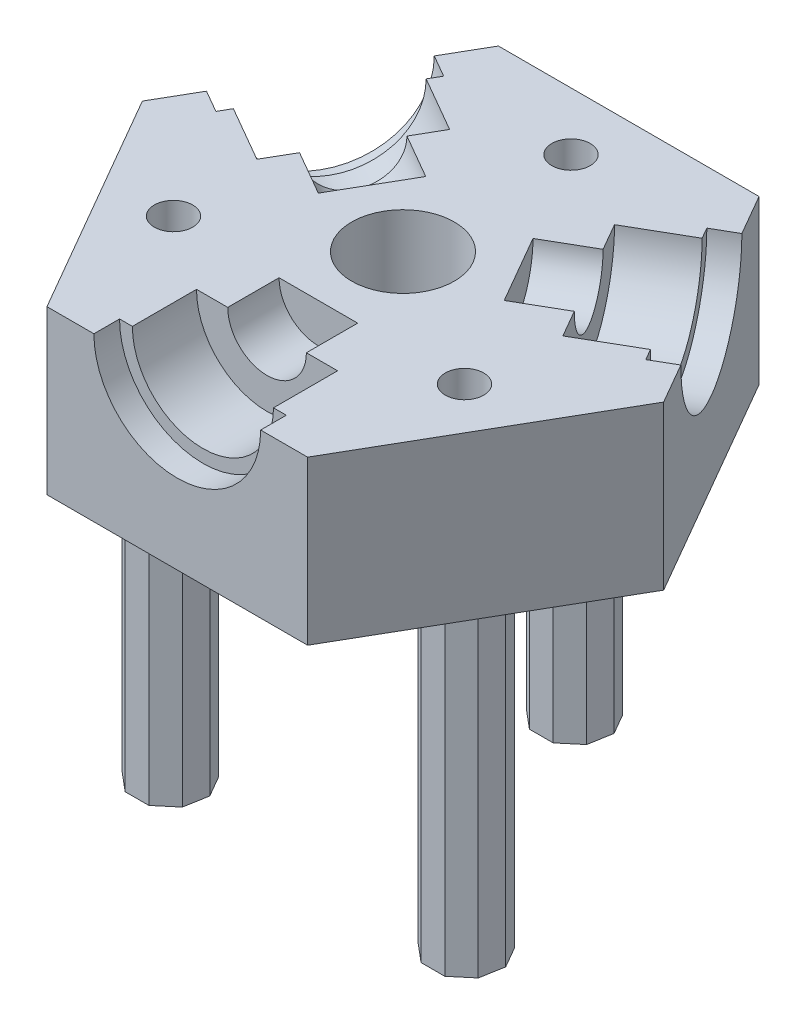
SolidWorks part; units mm, degrees
ref_plane "Front Plane" through (0, 0, 0) normal (0, 0, 1) x (1, 0, 0)
ref_plane "Top Plane" through (0, 0, 0) normal (0, 1, 0) x (1, 0, 0)
ref_plane "Right Plane" through (0, 0, 0) normal (1, 0, 0) x (0, 0, -1)
sketch "Sketch1" plane through (0, 0, 0) normal (0, 1, 0) x (1, 0, 0)
  line L1 (10.16, -17.5976) -> (20.32, 0)
  line L2 (20.32, 0) -> (10.16, 17.5976)
  line L3 (10.16, 17.5976) -> (-10.16, 17.5976)
  line L4 (-10.16, 17.5976) -> (-20.32, 0)
  line L5 (-20.32, 0) -> (-10.16, -17.5976)
  line L6 (-10.16, -17.5976) -> (10.16, -17.5976)
  circle A0 centre (0, 0) radius 17.5976 construction
  dimension "D1" = 20.32
extrude "Boss-Extrude1" add sketch "Sketch1" along normal blind 12.7 contours L4 L5 L6 L1 L2 L3
sketch "Sketch2" plane through (0, 0, 0) normal (0, -1, 0) x (1, 0, 0)
  circle A0 centre (0, 0) radius 4.1
  circle A1 centre (0, 0) radius 5.5
  dimension "D1" = 8.2
  dimension "D2" = 11
extrude "Boss-Extrude2" add sketch "Sketch2" along normal blind 3.5
sketch "Sketch5" plane through (0, 12.7, 0) normal (0, 1, 0) x (1, 0, 0)
  line L14 (0, -17.5976) -> (0, -6.5976)
  line L15 (-10.16, -17.5976) -> (10.16, -17.5976) construction
  line L16 (0, -6.5976) -> (-3.0653, -6.5976)
  line L17 (-3.0653, -6.5976) -> (-3.0653, -10.5976)
  line L18 (-3.0653, -10.5976) -> (-5.5, -10.5976)
  line L19 (-5.5, -10.5976) -> (-5.5, -15.5976)
  line L20 (-5.5, -15.5976) -> (-6.5, -15.5976)
  line L21 (-6.5, -15.5976) -> (-6.5, -17.5976)
  line L22 (-6.5, -17.5976) -> (0, -17.5976)
  dimension "D1" = 6.5
  dimension "D2" = 5.5
  dimension "D3" = 2
  dimension "D4" = 5
  dimension "D5" = 4
  dimension "D6" = 3.0653
revolve "Cut-Revolve1" cut sketch "Sketch5" angle 360 about L14
pattern_circular "CirPattern1" count 3 over 360 about axis through (0, -3.5, 0) along (0, 1, 0) of "Cut-Revolve1" reverse direction yes
sketch "Sketch6" plane through (0, 12.7, 0) normal (0, 1, 0) x (1, 0, 0)
  circle A0 centre (0, 0) radius 4
  dimension "D1" = 8
extrude "Cut-Extrude1" cut sketch "Sketch6" against normal through all
sketch "Random Circles" plane through (0, 12.7, 0) normal (0, 1, 0) x (1, 0, 0)
  line L0 (10.16, 17.5976) -> (-10.16, 17.5976) construction
  line L1 (-20.32, 0) -> (-10.16, -17.5976) construction
  line L2 (10.16, -17.5976) -> (20.32, 0) construction
  circle A0 centre (0, 13.0976) radius 1.5
  circle A1 centre (11.3429, -6.5488) radius 1.5
  circle A2 centre (-11.3429, -6.5488) radius 1.5
  point P11 (0, 0)
  dimension "D1" = 3
  dimension "D2" = 3
  dimension "D4" = 3
  dimension "D5" = 3
  dimension "D3" = 3
sketch "Sketch8" plane through (0, 0, 0) normal (0, 1, 0) x (1, 0, 0)
  line L9 (10.16, 17.5976) -> (-10.16, 17.5976) construction
  line L19 (-1.7375, 15.3916) -> (-2.6619, 13.7904)
  line L20 (-2.6619, 13.7904) -> (-2.3409, 11.9695)
  line L21 (-2.3409, 11.9695) -> (-0.9245, 10.781)
  line L22 (-0.9245, 10.781) -> (0.9245, 10.781)
  line L23 (0.9245, 10.781) -> (2.3409, 11.9695)
  line L24 (2.3409, 11.9695) -> (2.6619, 13.7904)
  line L25 (2.6619, 13.7904) -> (1.7375, 15.3916)
  line L26 (1.7375, 15.3916) -> (0, 16.024)
  line L27 (0, 16.024) -> (-1.7375, 15.3916)
  line L28 (14.1983, -6.1911) -> (13.2738, -4.5899)
  line L29 (13.2738, -4.5899) -> (11.5363, -3.9575)
  line L30 (11.5363, -3.9575) -> (9.7989, -4.5899)
  line L31 (9.7989, -4.5899) -> (8.8744, -6.1911)
  line L32 (8.8744, -6.1911) -> (9.1954, -8.012)
  line L33 (9.1954, -8.012) -> (10.6118, -9.2005)
  line L34 (10.6118, -9.2005) -> (12.4608, -9.2005)
  line L35 (12.4608, -9.2005) -> (13.8772, -8.012)
  line L36 (13.8772, -8.012) -> (14.1983, -6.1911)
  line L37 (-12.4608, -9.2005) -> (-10.6118, -9.2005)
  line L38 (-10.6118, -9.2005) -> (-9.1954, -8.012)
  line L39 (-9.1954, -8.012) -> (-8.8744, -6.1911)
  line L40 (-8.8744, -6.1911) -> (-9.7989, -4.5899)
  line L41 (-9.7989, -4.5899) -> (-11.5363, -3.9575)
  line L42 (-11.5363, -3.9575) -> (-13.2738, -4.5899)
  line L43 (-13.2738, -4.5899) -> (-14.1983, -6.1911)
  line L44 (-14.1983, -6.1911) -> (-13.8772, -8.012)
  line L45 (-13.8772, -8.012) -> (-12.4608, -9.2005)
  circle A0 centre (11.5363, -6.6605) radius 2.54 construction
  circle A1 centre (-11.5363, -6.6605) radius 2.54 construction
  circle A2 centre (0, 13.321) radius 2.54 construction
  point P0 (0, 17.5976)
  point P37 (0, 0)
  dimension "D1" = 23.0726
  dimension "D2" = 3
  dimension "D6" = 5.08
  dimension "D3" = 1.5736
extrude "Boss-Extrude3" add sketch "Sketch8" against normal blind 25.4
extrude "Cut-Extrude2" cut sketch "Random Circles" against normal blind 2.54
